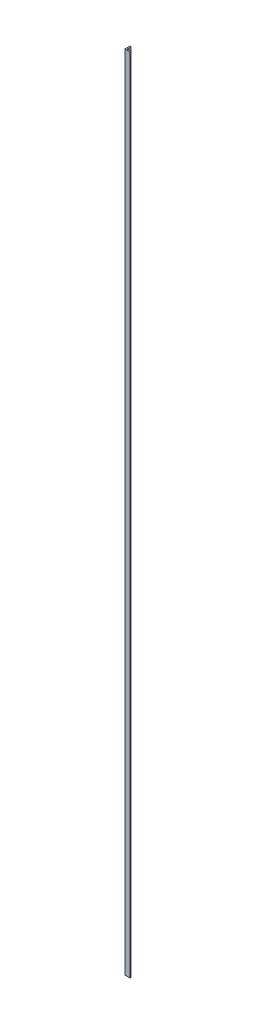
SolidWorks part; units mm, degrees
material "S235 JR"
ref_plane "FACE" through (0, 0, 0) normal (0, 0, 1) x (1, 0, 0)
ref_plane "DESSUS" through (0, 0, 0) normal (0, 1, 0) x (1, 0, 0)
ref_plane "DROITE" through (0, 0, 0) normal (1, 0, 0) x (0, 0, -1)
sketch "Esquisse2" plane through (0, 0, 0) normal (0, 1, 0) x (1, 0, 0)
  line L0 (0, 13) -> (0, 0)
  line L1 (0, 0) -> (13, 0)
  line L2 (13, 0) -> (13, 3)
  line L3 (13, 3) -> (4.5, 3)
  line L4 (3, 4.5) -> (3, 13)
  line L5 (3, 13) -> (0, 13)
  arc A0 (4.5, 3) -> (3, 4.5) centre (4.5, 4.5) cw
  dimension "D1" = 13
  dimension "D4" = 1.5
  dimension "D2" = 3
  dimension "D3" = 3
  dimension "D5" = 13
extrude "Boss.-Extru.1" add sketch "Esquisse2" along normal blind 2017
